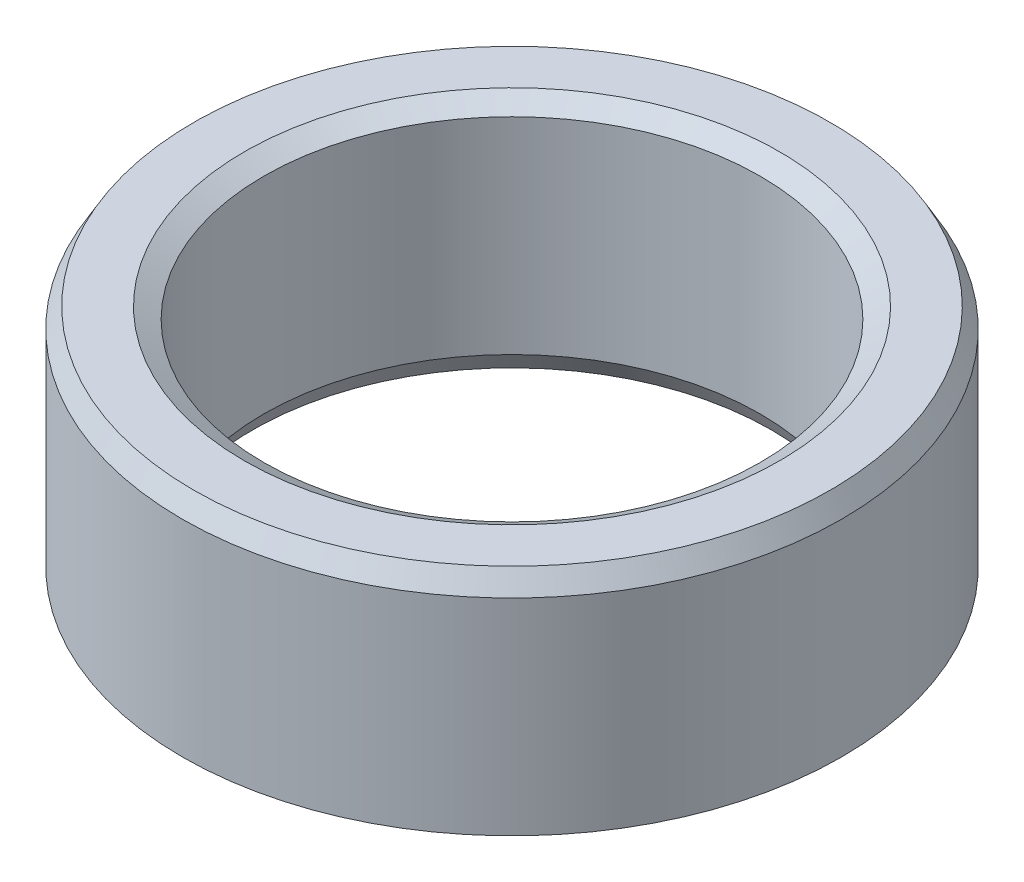
SolidWorks part; units mm, degrees
ref_plane "Front Plane" through (0, 0, 0) normal (0, 0, 1) x (1, 0, 0)
ref_plane "Top Plane" through (0, 0, 0) normal (0, 1, 0) x (1, 0, 0)
ref_plane "Right Plane" through (0, 0, 0) normal (1, 0, 0) x (0, 0, -1)
sketch "Sketch1" plane through (0, 0, 0) normal (0, 1, 0) x (1, 0, 0)
  circle A0 centre (0, 0) radius 40
  dimension "SLEEVE_OD" = 80
extrude "Boss-Extrude1" add sketch "Sketch1" along normal blind 28.7259
sketch "Sketch2" plane through (0, 0, 0) normal (0, 1, 0) x (1, 0, 0)
  circle A0 centre (0, 0) radius 30.1032
  dimension "BORE_D" = 60.2063
extrude "Cut-Extrude1" cut sketch "Sketch2" along normal through all
chamfer "Chamfer1" distance 2.3723 angle 30 4 edges at (0, 28.7259, 30.1032) (0, 0, 30.1032) (0, 0, 40) (0, 28.7259, 40) first distance on face at (0, 28.7259, 30.1032) first distance on face at (0, 0, 30.1032) first distance on face at (0, 28.7259, 40)
